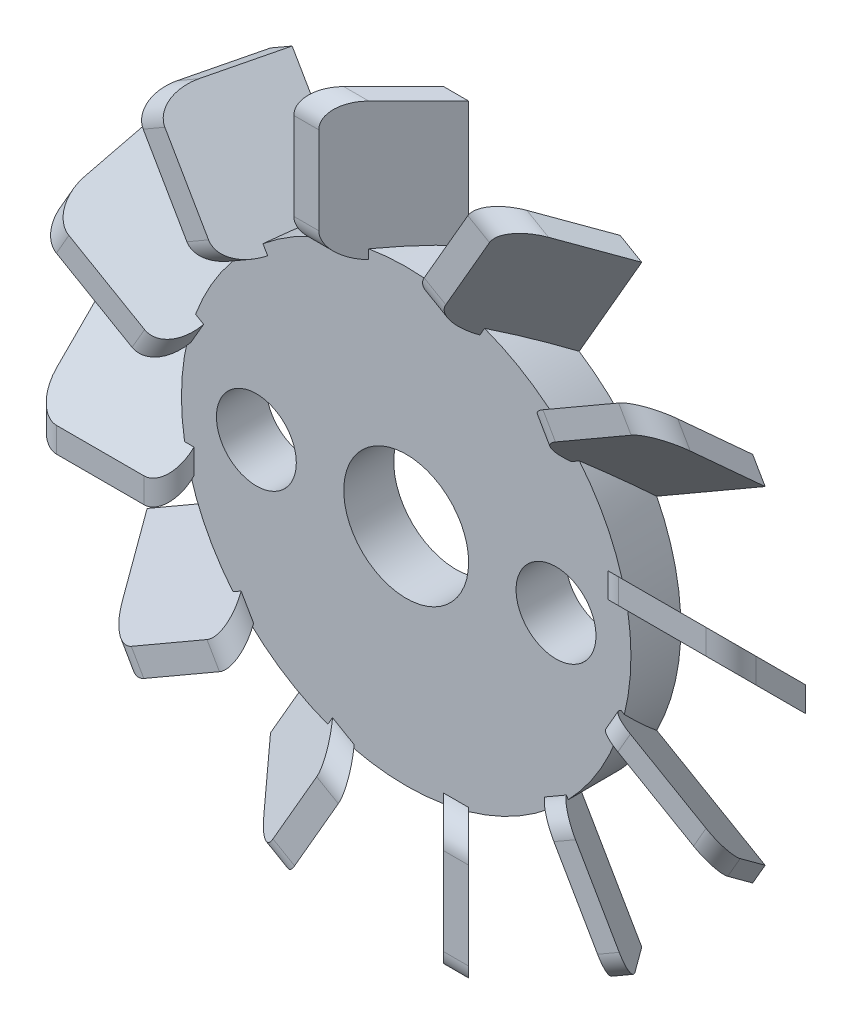
SolidWorks part; units mm, degrees
material "ABS"
ref_plane "Front Plane" through (0, 0, 0) normal (0, 0, 1) x (1, 0, 0)
ref_plane "Top Plane" through (0, 0, 0) normal (0, 1, 0) x (1, 0, 0)
ref_plane "Right Plane" through (0, 0, 0) normal (1, 0, 0) x (0, 0, -1)
ref_axis "X" through (-18.7, 0, 0) along (1, 0, 0)
ref_axis "Y" through (0, 18.7, 0) along (0, -1, 0)
ref_axis "Z" through (0, 0, -0.15) along (0, 0, 1)
sketch "Sketch1" plane through (0, 0, 0) normal (0, 0, 1) x (1, 0, 0)
  line L0 (-6, 0) -> (6, 0) construction
  circle A0 centre (0, 0) radius 2.5
  circle A1 centre (0, 0) radius 9
  circle A2 centre (6, 0) radius 3 construction
  circle A3 centre (-6, 0) radius 3 construction
  point P6 (0, 0)
  point P8 (9, 0)
  dimension "D1" = 5
  dimension "D3" = 6
  dimension "D2" = 6
sketch "Sketch2" plane through (0, 0, 0) normal (1, 0, 0) x (0, 0, -1)
  line L0 (0, 0.5) -> (0, -0.5)
  line L2 (0, 0.5) -> (-3, 3.5)
  line L3 (-3, 3.5) -> (-3, 2.5)
  line L4 (-3, 2.5) -> (0, -0.5)
  line L5 (0, 0) -> (-2, 0) construction
  point P6 (0, 0)
  dimension "D1" = 1
  dimension "D2" = 135
  dimension "D3" = 2
  dimension "D4" = 3
extrude "Boss-Extrude1" add sketch "Sketch1" along normal up to vertex (2 mm away) up to point (0, 0, 2)
extrude "Boss-Extrude2" add sketch "Sketch2" along normal blind 5 and the other way blind 0.5 from vertex starting at point (9, 0, 0)
fillet "Fillet1" radius 1 2 edges at (8.5, 3, 3) (14, 3, 3)
pattern_circular "CirPattern1" count 12 over 360 about axis through (0, 0, -0.15) along (0, 0, 1) of "Boss-Extrude2", "Fillet1"
sketch "Sketch5" plane through (0, 0, 2) normal (0, 0, 1) x (1, 0, 0)
  point P0 (-6, 0)
  point P3 (6, 0)
hole_wizard "M3 Clearance Hole1" positions "Sketch5" profile "Sketch4" hole size "M3" standard "ANSI Metric" end condition through all
sketch "Sketch4" plane through (-6, 0, 2) normal (1, 0, 0) x (0, -1, 0)
  line L0 (0, 0) -> (0, 2)
  line L1 (0, 2) -> (1.6, 2)
  line L2 (1.6, 2) -> (1.6, 0)
  line L5 (1.6, 0) -> (0, 0)
  line L11 (0, -6.35) -> (0, 107.95) construction
  dimension "Thru Hole Dia." = 3.2
  dimension "Thru Hole Depth" = 2
